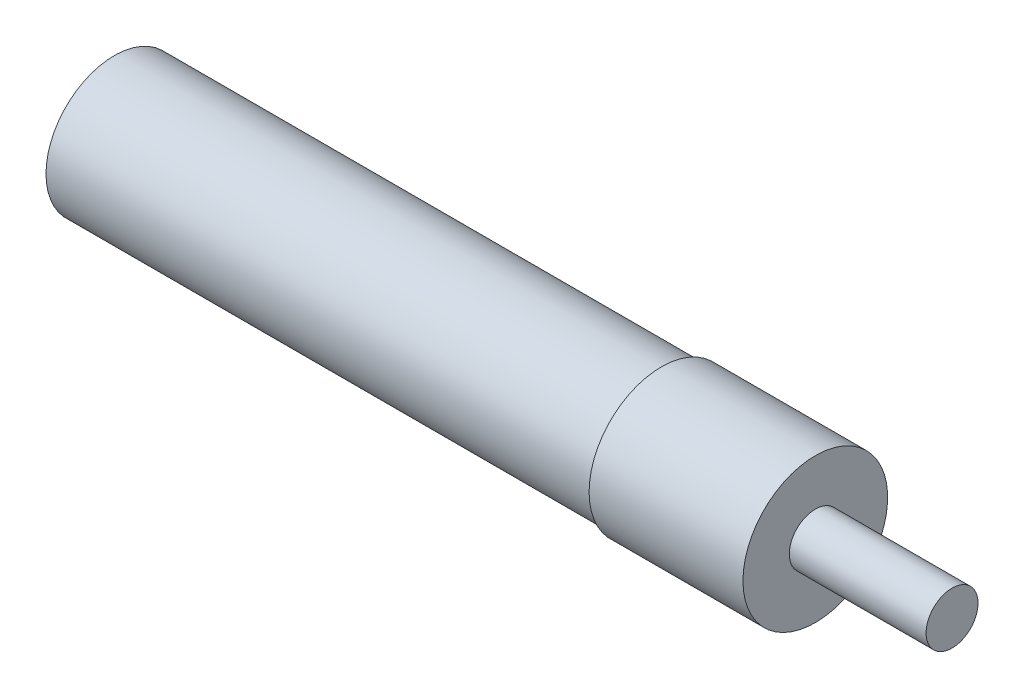
SolidWorks part; units mm, degrees
ref_plane "Front Plane" through (0, 0, 0) normal (0, 0, 1) x (1, 0, 0)
ref_plane "Top Plane" through (0, 0, 0) normal (0, 1, 0) x (1, 0, 0)
ref_plane "Right Plane" through (0, 0, 0) normal (1, 0, 0) x (0, 0, -1)
sketch "Sketch2" plane through (0, 0, 0) normal (0, 0, 1) x (1, 0, 0)
  line L0 (0, 0) -> (0, 6.35)
  line L1 (0, 6.35) -> (50.8, 6.35)
  line L2 (50.8, 6.35) -> (50.8, 6.7183)
  line L3 (50.8, 6.7183) -> (65.0875, 6.7183)
  line L4 (65.0875, 6.7183) -> (65.0875, 2.413)
  line L5 (65.0875, 2.413) -> (77.7875, 2.413)
  line L6 (77.7875, 2.413) -> (77.7875, 0)
  line L7 (0, 0) -> (77.7875, 0)
  dimension "D1" = 6.35
  dimension "D2" = 50.8
  dimension "D3" = 14.2875
  dimension "D4" = 12.7
  dimension "D5" = 6.7183
  dimension "D6" = 2.413
revolve "Revolve1" add sketch "Sketch2" angle 360 about L7
